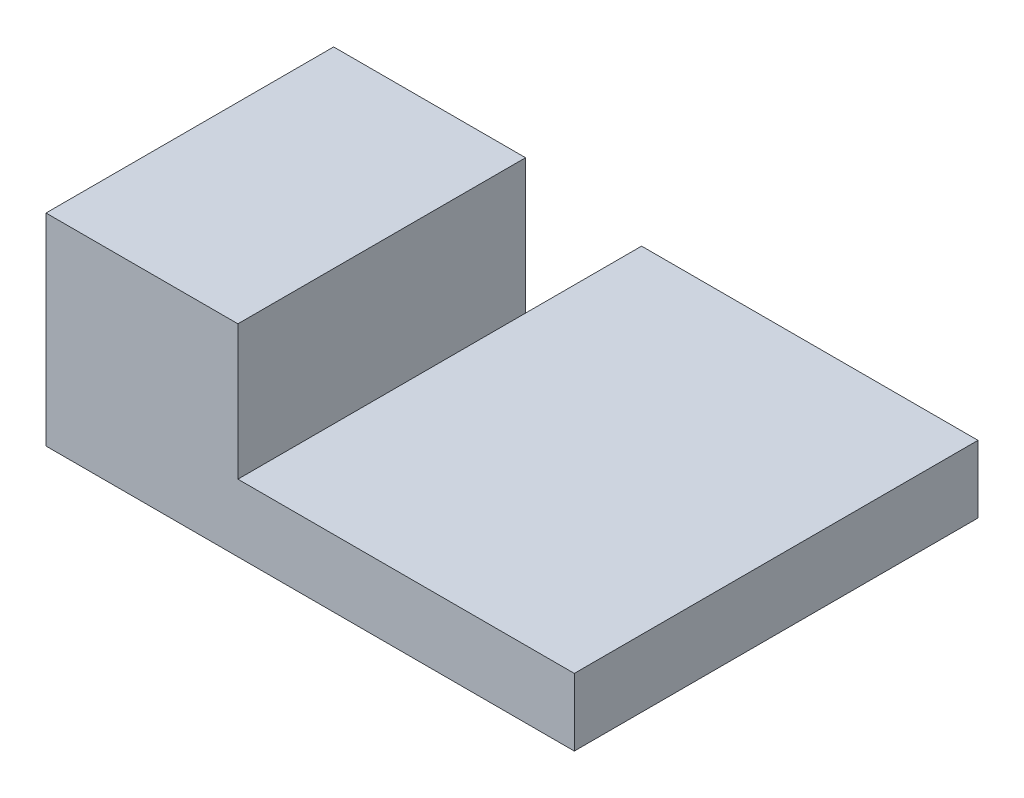
SolidWorks part; units mm, degrees
ref_plane "Front Plane" through (0, 0, 0) normal (0, 0, 1) x (1, 0, 0)
ref_plane "Top Plane" through (0, 0, 0) normal (0, 1, 0) x (1, 0, 0)
ref_plane "Right Plane" through (0, 0, 0) normal (1, 0, 0) x (0, 0, -1)
sketch "Sketch1" plane through (0, 0, 0) normal (0, 1, 0) x (1, 0, 0)
  line L1 (-25, 30) -> (25, 30)
  line L2 (-25, 30) -> (-25, -30)
  line L3 (-25, -30) -> (25, -30)
  line L4 (25, 30) -> (25, -30)
  line L5 (-25, 30) -> (25, -30) construction
  line L6 (-25, -30) -> (25, 30) construction
  line L7 (-25, 12.7546) -> (-53.5221, 12.7546)
  line L8 (-25, 12.7546) -> (-25, -30)
  line L9 (-25, -30) -> (-53.5221, -30)
  line L10 (-53.5221, 12.7546) -> (-53.5221, -30)
  point P0 (0, 0)
extrude "Boss-Extrude1" add sketch "Sketch1" along normal blind 10 contours L4 L1 L2 L3 region at (0, 0, 0)
extrude "Boss-Extrude2" add sketch "Sketch1<3>" along normal blind 30 contours L7 L10 L9 L2 region at (-39.261, 0, 8.6227)
sketch "Sketch1<3>" plane through (0, 0, 0) normal (0, 1, 0) x (1, 0, 0) same geometry as "Sketch1"
